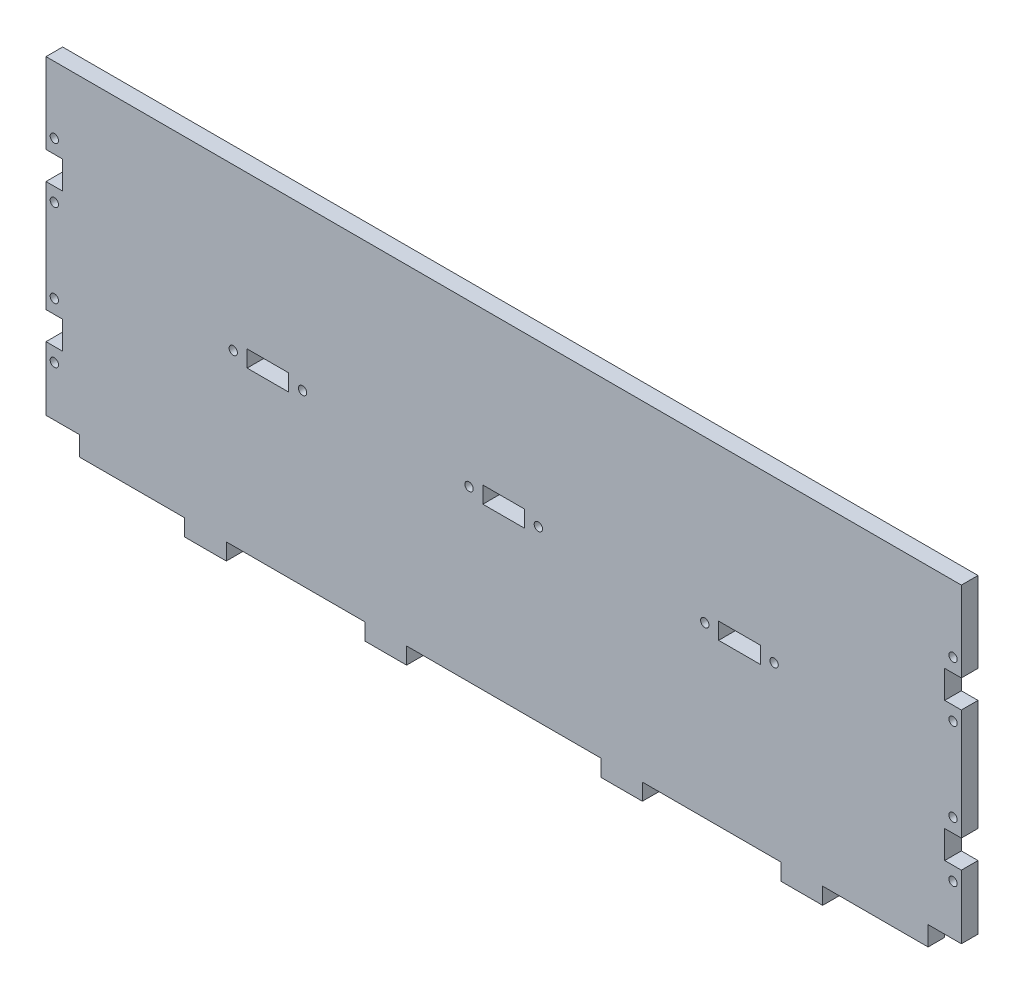
SolidWorks part; units mm, degrees
ref_plane "Plan de face" through (0, 0, 0) normal (0, 0, 1) x (1, 0, 0)
ref_plane "Plan de dessus" through (0, 0, 0) normal (0, 1, 0) x (1, 0, 0)
ref_plane "Plan de droite" through (0, 0, 0) normal (1, 0, 0) x (0, 0, -1)
sketch "Esquisse1" plane through (0, 0, 0) normal (0, 0, 1) x (1, 0, 0)
  line L0 (97.3951, 0) -> (-118.5049, 0) construction
  line L1 (-165, 119) -> (165, 119)
  line L2 (-165, 119) -> (-165, -119)
  line L3 (-165, -119) -> (165, -119)
  line L4 (165, 119) -> (165, -119)
  line L5 (0, 79.3588) -> (0, -79.3588) construction
  line L6 (-92.5, -55) -> (-77.5, -55)
  line L7 (-92.5, -55) -> (-92.5, -61)
  line L8 (-92.5, -61) -> (-77.5, -61)
  line L9 (-77.5, -55) -> (-77.5, -61)
  line L10 (-7.5, -55) -> (7.5, -55)
  line L11 (-7.5, -55) -> (-7.5, -61)
  line L12 (-7.5, -61) -> (7.5, -61)
  line L13 (7.5, -55) -> (7.5, -61)
  line L14 (77.5, -55) -> (92.5, -55)
  line L15 (77.5, -55) -> (77.5, -61)
  line L16 (77.5, -61) -> (92.5, -61)
  line L17 (92.5, -55) -> (92.5, -61)
  dimension "D1" = 238
  dimension "D2" = 330
  dimension "D3" = 165
  dimension "D4" = 119
  dimension "D5" = 15
  dimension "D6" = 6
  dimension "D7" = 6
  dimension "D8" = 15
  dimension "D9" = 6
  dimension "D10" = 15
  dimension "D11" = 70
  dimension "D12" = 70
  dimension "D13" = 58
  dimension "D14" = 72.5
extrude "Boss.-Extru.1" add sketch "Esquisse1" along normal blind 6
sketch "Esquisse2" plane through (0, 0, 6) normal (0, 0, 1) x (1, 0, 0)
  line L0 (243.146, 0) -> (-260.0003, 0) construction
  line L1 (0, 180.4713) -> (0, -129.6072) construction
  line L2 (165, 119) -> (-165, 119) construction
  line L3 (-115, 119) -> (-100, 119)
  line L4 (-115, 119) -> (-115, 125)
  line L5 (-115, 125) -> (-100, 125)
  line L6 (-100, 119) -> (-100, 125)
  line L7 (-165, 119) -> (-165, -119) construction
  line L8 (-50, 119) -> (-35, 119)
  line L9 (-50, 119) -> (-50, 125)
  line L10 (-50, 125) -> (-35, 125)
  line L11 (-35, 119) -> (-35, 125)
  line L12 (35, 119) -> (35, 125)
  line L13 (50, 125) -> (35, 125)
  line L14 (50, 119) -> (50, 125)
  line L15 (50, 119) -> (35, 119)
  line L16 (100, 119) -> (100, 125)
  line L17 (115, 125) -> (100, 125)
  line L18 (115, 119) -> (115, 125)
  line L19 (115, 119) -> (100, 119)
  line L20 (-115, 119) -> (-100, 119)
  line L21 (-115, 119) -> (-115, 125)
  line L22 (-115, 125) -> (-100, 125)
  line L23 (-100, 119) -> (-100, 125)
  line L24 (-50, 119) -> (-35, 119)
  line L25 (-50, 119) -> (-50, 125)
  line L26 (-50, 125) -> (-35, 125)
  line L27 (-35, 119) -> (-35, 125)
  line L28 (35, 119) -> (35, 125)
  line L29 (50, 125) -> (35, 125)
  line L30 (50, 119) -> (50, 125)
  line L31 (50, 119) -> (35, 119)
  line L32 (100, 119) -> (100, 125)
  line L33 (115, 125) -> (100, 125)
  line L34 (115, 119) -> (115, 125)
  line L35 (115, 119) -> (100, 119)
  line L36 (115, -119) -> (100, -119)
  line L37 (115, -119) -> (115, -125)
  line L38 (115, -125) -> (100, -125)
  line L39 (100, -119) -> (100, -125)
  line L40 (50, -119) -> (35, -119)
  line L41 (50, -119) -> (50, -125)
  line L42 (50, -125) -> (35, -125)
  line L43 (35, -119) -> (35, -125)
  line L44 (-35, -119) -> (-35, -125)
  line L45 (-50, -125) -> (-35, -125)
  line L46 (-50, -119) -> (-50, -125)
  line L47 (-50, -119) -> (-35, -119)
  line L48 (-100, -119) -> (-100, -125)
  line L49 (-115, -125) -> (-100, -125)
  line L50 (-115, -119) -> (-115, -125)
  line L51 (-115, -119) -> (-100, -119)
  line L52 (115, -119) -> (100, -119)
  line L53 (115, -119) -> (115, -125)
  line L54 (115, -125) -> (100, -125)
  line L55 (100, -119) -> (100, -125)
  line L56 (50, -119) -> (35, -119)
  line L57 (50, -119) -> (50, -125)
  line L58 (50, -125) -> (35, -125)
  line L59 (35, -119) -> (35, -125)
  line L60 (-35, -119) -> (-35, -125)
  line L61 (-50, -125) -> (-35, -125)
  line L62 (-50, -119) -> (-50, -125)
  line L63 (-50, -119) -> (-35, -119)
  line L64 (-100, -119) -> (-100, -125)
  line L65 (-115, -125) -> (-100, -125)
  line L66 (-115, -119) -> (-115, -125)
  line L67 (-115, -119) -> (-100, -119)
  line M9 (-165, -119) -> (165, -119)
  line M11 (165, 119) -> (-165, 119)
  dimension "D1" = 6
  dimension "D2" = 6
  dimension "D3" = 15
  dimension "D4" = 15
  dimension "D5" = 50
  dimension "D6" = 50
extrude "Boss.-Extru.2" add sketch "Esquisse2" against normal blind 6 contours L6 L5 L4 M11 | L11 L10 L9 M11 | L14 L13 L12 M11 | L18 L17 L16 M11 | L39 L38 L37 M9 | L43 L42 L41 M9 | L46 L45 L44 M9 | L50 L49 L48 M9 region at (-107.5, 122, 6) region at (107.5, 122, 6) region at (42.5, 122, 6) region at (-42.5, 122, 6) region at (107.5, -122, 6) region at (-107.5, -122, 6) region at (-42.5, -122, 6) region at (42.5, -122, 6)
sketch "Esquisse3" plane through (0, 0, 6) normal (0, 0, 1) x (1, 0, 0)
  line L0 (-165, 119) -> (-165, -119) construction
  line L1 (-165, 79) -> (-159, 79)
  line L2 (-165, 79) -> (-165, 89)
  line L3 (-165, 89) -> (-159, 89)
  line L4 (-159, 79) -> (-159, 89)
  line L5 (234.1368, 0) -> (-337.9213, 0) construction
  line L6 (-165, 39) -> (-159, 39)
  line L7 (-165, 39) -> (-165, 29)
  line L8 (-165, 29) -> (-159, 29)
  line L9 (-159, 39) -> (-159, 29)
  line L10 (0, 279.7488) -> (0, -188.1201) construction
  line L11 (-115, 119) -> (-165, 119) construction
  line L12 (-159, -39) -> (-159, -29)
  line L13 (-165, -29) -> (-159, -29)
  line L14 (-165, -39) -> (-165, -29)
  line L15 (-165, -39) -> (-159, -39)
  line L16 (-159, -79) -> (-159, -89)
  line L17 (-165, -89) -> (-159, -89)
  line L18 (-165, -79) -> (-165, -89)
  line L19 (-165, -79) -> (-159, -79)
  line L20 (165, -79) -> (159, -79)
  line L21 (165, -79) -> (165, -89)
  line L22 (165, -89) -> (159, -89)
  line L23 (159, -79) -> (159, -89)
  line L24 (165, -39) -> (159, -39)
  line L25 (165, -39) -> (165, -29)
  line L26 (165, -29) -> (159, -29)
  line L27 (159, -39) -> (159, -29)
  line L28 (159, 39) -> (159, 29)
  line L29 (165, 29) -> (159, 29)
  line L30 (165, 39) -> (165, 29)
  line L31 (165, 39) -> (159, 39)
  line L32 (159, 79) -> (159, 89)
  line L33 (165, 89) -> (159, 89)
  line L34 (165, 79) -> (165, 89)
  line L35 (165, 79) -> (159, 79)
  line L36 (153, -119) -> (153, -112)
  line L37 (-165, -119) -> (-153, -119)
  line L38 (-165, -119) -> (-165, -112)
  line L39 (-165, -112) -> (-153, -112)
  line L40 (-153, -119) -> (-153, -112)
  line L41 (165, -112) -> (153, -112)
  line L42 (165, -119) -> (165, -112)
  line L43 (165, -119) -> (153, -119)
  dimension "D1" = 40
  dimension "D2" = 6
  dimension "D3" = 6
  dimension "D4" = 10
  dimension "D5" = 10
  dimension "D6" = 30
  dimension "D7" = 12
  dimension "D8" = 7
extrude "Enlèv. mat.-Extru.1" cut sketch "Esquisse3" against normal blind 6
sketch "Esquisse4" plane through (0, 0, 6) normal (0, 0, 1) x (1, 0, 0)
  line L0 (-162, 121.7279) -> (-162, -131.0602) construction
  line L1 (0, 158.5579) -> (0, -182.4489) construction
  line L2 (-115, 119) -> (-165, 119) construction
  line L3 (-106.4439, -58) -> (117.3944, -58) construction
  line L4 (-159, 89) -> (-165, 89) construction
  line L5 (-165, 119) -> (-165, 89) construction
  line L6 (-165, 79) -> (-159, 79) construction
  line L7 (-159, 39) -> (-165, 39) construction
  line L8 (-165, 29) -> (-159, 29) construction
  line L9 (-159, -29) -> (-165, -29) construction
  line L10 (-92.5, -55) -> (-92.5, -61) construction
  line L11 (-77.5, -61) -> (-77.5, -55) construction
  line L12 (-165, -39) -> (-159, -39) construction
  line L13 (-159, -79) -> (-165, -79) construction
  line L14 (-165, -89) -> (-159, -89) construction
  line L15 (-7.5, -55) -> (-7.5, -61) construction
  line L16 (162, 121.7279) -> (162, -131.0602) construction
  circle A0 centre (-162, 114) radius 1.5
  circle A1 centre (-162, 94) radius 1.5
  circle A2 centre (-162, 74) radius 1.5
  circle A3 centre (-162, 44) radius 1.5
  circle A4 centre (-162, 24) radius 1.5
  circle A6 centre (-162, -24) radius 1.5
  circle A7 centre (-162, -44) radius 1.5
  circle A8 centre (-162, -74) radius 1.5
  circle A9 centre (-162, -94) radius 1.5
  circle A10 centre (-97.5, -58) radius 1.5
  circle A11 centre (-72.5, -58) radius 1.5
  circle A12 centre (162, -94) radius 1.5
  circle A13 centre (162, -74) radius 1.5
  circle A14 centre (162, -44) radius 1.5
  circle A15 centre (162, -24) radius 1.5
  circle A17 centre (162, 24) radius 1.5
  circle A18 centre (162, 44) radius 1.5
  circle A19 centre (162, 74) radius 1.5
  circle A20 centre (162, 94) radius 1.5
  circle A21 centre (162, 114) radius 1.5
  circle A22 centre (-12.5, -58) radius 1.5
  circle A23 centre (12.5, -58) radius 1.5
  circle A24 centre (72.5, -58) radius 1.5
  circle A25 centre (97.5, -58) radius 1.5
  dimension "D1" = 3
  dimension "D2" = 3
  dimension "D3" = 3
  dimension "D4" = 3
  dimension "D5" = 3
  dimension "D7" = 3
  dimension "D8" = 3
  dimension "D9" = 3
  dimension "D10" = 3
  dimension "D11" = 3
  dimension "D12" = 5
  dimension "D13" = 5
  dimension "D15" = 5
  dimension "D16" = 5
  dimension "D17" = 5
  dimension "D20" = 5
  dimension "D21" = 5
  dimension "D23" = 3
  dimension "D24" = 3
  dimension "D25" = 5
  dimension "D26" = 5
  dimension "D27" = 5
  dimension "D14" = 3
  dimension "D18" = 5
  dimension "D22" = 5
extrude "Enlèv. mat.-Extru.2" cut sketch "Esquisse4" against normal blind 6
sketch "Esquisse5" plane through (0, 0, 6) normal (0, 0, 1) x (1, 0, 0)
  line L1 (-174.9982, 0) -> (181.1877, 0)
  line L2 (-174.9982, 0) -> (-174.9982, 137.1433)
  line L3 (-174.9982, 137.1433) -> (181.1877, 137.1433)
  line L4 (181.1877, 0) -> (181.1877, 137.1433)
extrude "Enlèv. mat.-Extru.3" cut sketch "Esquisse5" against normal blind 6
equation "\"D3@Esquisse1\"=\"D2@Esquisse1\"/2"
equation "\"D4@Esquisse1\"=\"D1@Esquisse1\"/2"
